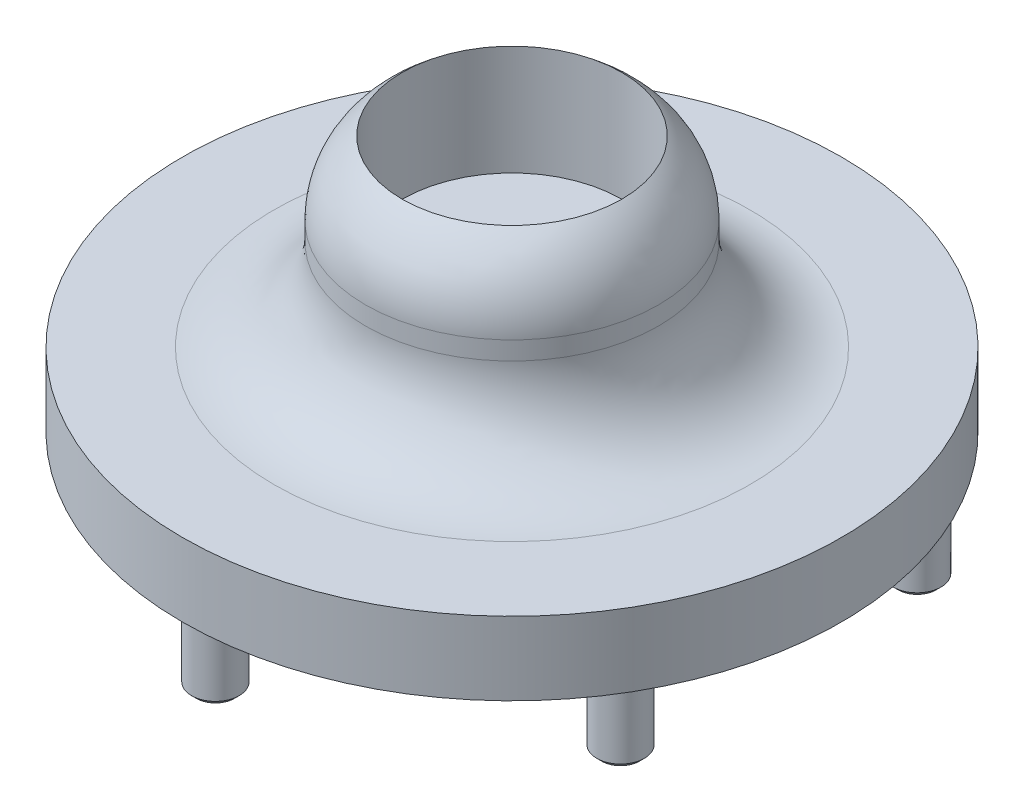
SolidWorks part; units mm, degrees
ref_plane "Front Plane" through (0, 0, 0) normal (0, 0, 1) x (1, 0, 0)
ref_plane "Top Plane" through (0, 0, 0) normal (0, 1, 0) x (1, 0, 0)
ref_plane "Right Plane" through (0, 0, 0) normal (1, 0, 0) x (0, 0, -1)
sketch "Sketch1" plane through (0, 0, 0) normal (0, 0, 1) x (1, 0, 0)
  line L0 (0, 0) -> (-45, 0)
  line L1 (-45, 0) -> (-45, 45)
  line L2 (-45, 45) -> (-75, 45)
  line L3 (-75, 45) -> (-75, 59.0741)
  line L4 (-75, 59.0741) -> (-135, 59.0741)
  line L5 (-135, 59.0741) -> (-135, 89.0741)
  line L6 (-135, 89.0741) -> (-60, 89.0741)
  line L7 (-60, 89.0741) -> (-60, 164.0741)
  line L8 (-60, 164.0741) -> (-45, 164.0741)
  line L9 (-45, 164.0741) -> (-45, 119.0741)
  line L10 (-45, 119.0741) -> (0, 119.0741)
  line L11 (0, 119.0741) -> (0, 0)
  dimension "D1" = 45
  dimension "D2" = 45
  dimension "D3" = 60
  dimension "D4" = 30
  dimension "D5" = 75
  dimension "D6" = 75
  dimension "D7" = 15
  dimension "D8" = 45
  dimension "D9" = 45
revolve "Revolve1" add sketch "Sketch1" angle 360 about L11
sketch "Sketch2" plane through (0, 89.0741, 0) normal (0, 1, 0) x (1, 0, 0)
  circle A0 centre (0, 121.5) radius 9.75
  dimension "D1" = 121.5
  dimension "D2" = 19.5
fillet "Fillet1" radius 37.5 2 edges at (0, 164.0741, 60) (0, 89.0741, 60)
fillet "Fillet6" radius 37.5 1 edges at (0, 45, 45)
fillet "Fillet8" radius 22.5 1 edges at (0, 0, 45)
sketch "Sketch4" plane through (0, 59.0741, 0) normal (0, -1, 0) x (1, 0, 0)
  circle A0 centre (0, 121.5) radius 9.75
  dimension "D1" = 19.5
  dimension "D2" = 121.5
extrude "Boss-Extrude2" add sketch "Sketch4" along normal blind 30
chamfer "Chamfer1" distance 2 angle 45 1 edges at (0, 29.0741, 111.75)
pattern_circular "CirPattern4" count 6 over 360 about axis through (0, 119.0741, 0) along (0, 1, 0) of "Chamfer1", "Boss-Extrude2"
